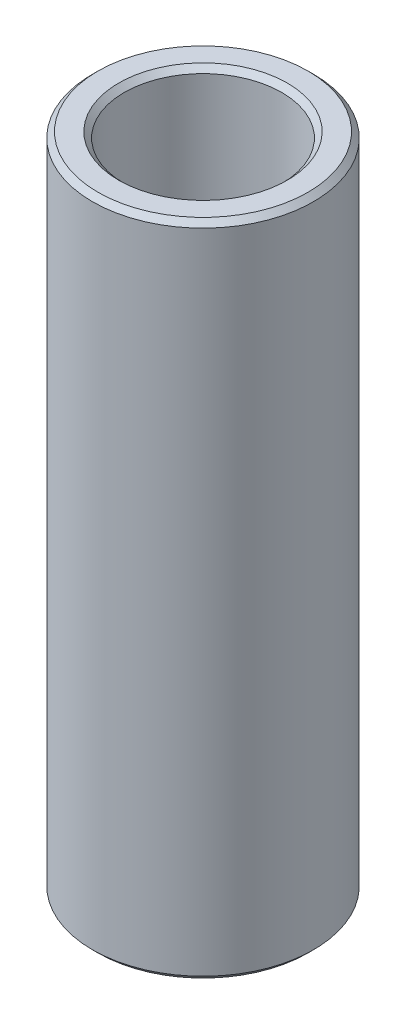
SolidWorks part; units mm, degrees
ref_plane "Front Plane" through (0, 0, 0) normal (0, 0, 1) x (1, 0, 0)
ref_plane "Top Plane" through (0, 0, 0) normal (0, 1, 0) x (1, 0, 0)
ref_plane "Right Plane" through (0, 0, 0) normal (1, 0, 0) x (0, 0, -1)
sketch "Sketch1" plane through (0, 0, 0) normal (0, 1, 0) x (1, 0, 0)
  circle A0 centre (0, 0) radius 12.5
  dimension "SLEEVE_OD" = 25
extrude "Boss-Extrude1" add sketch "Sketch1" along normal blind 74.525
sketch "Sketch2" plane through (0, 0, 0) normal (0, 1, 0) x (1, 0, 0)
  circle A0 centre (0, 0) radius 8.9156
  dimension "BORE_D" = 17.8313
extrude "Cut-Extrude1" cut sketch "Sketch2" along normal through all
chamfer "Chamfer1" distance 0.618 angle 45 4 edges at (0, 74.525, 8.9156) (0, 0, 8.9156) (0, 0, 12.5) (0, 74.525, 12.5)
